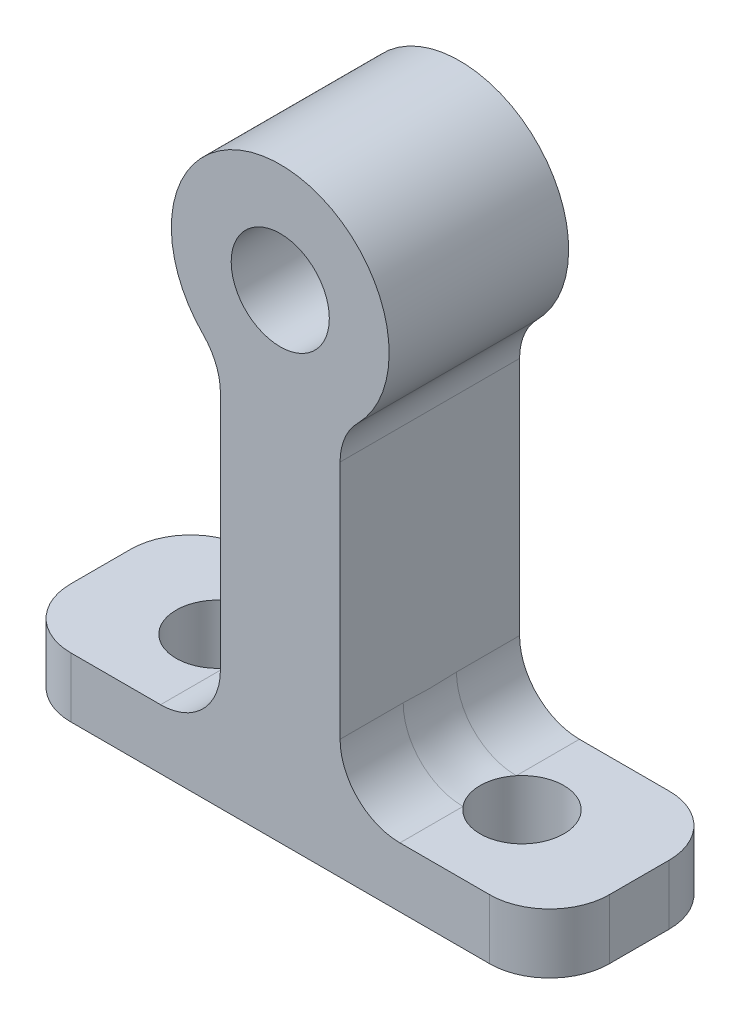
SolidWorks part; units mm, degrees
ref_plane "Front Plane" through (0, 0, 0) normal (0, 0, 1) x (1, 0, 0)
ref_plane "Top Plane" through (0, 0, 0) normal (0, 1, 0) x (1, 0, 0)
ref_plane "Right Plane" through (0, 0, 0) normal (1, 0, 0) x (0, 0, -1)
sketch "Sketch1" plane through (0, 0, 0) normal (0, 0, 1) x (1, 0, 0)
  line L0 (-5, -7.6033) -> (-5, -35)
  line L1 (5, -7.6033) -> (5, -35)
  line L10 (-22.5, -35) -> (-22.5, -40)
  line L11 (-22.5, -40) -> (22.5, -40)
  line L12 (22.5, -35) -> (22.5, -40)
  line L13 (-22.5, -35) -> (-5, -35)
  line L14 (22.5, -35) -> (5, -35)
  arc A1 (5, -7.6033) -> (-5, -7.6033) centre (0, 0) ccw
  circle A2 centre (0, 0) radius 4.1
  point P11 (-7.5, -6.6854)
  dimension "D1" = 8.2
  dimension "D2" = 45
  dimension "D5" = 5
  dimension "D6" = 5
  dimension "D3" = 40
  dimension "D4" = 10
extrude "Boss-Extrude1" add sketch "Sketch1" along normal blind 15
sketch "Sketch4" plane through (0, 0, 0) normal (0, 0, -1) x (-1, 0, 0)
  circle A0 centre (0, 0) radius 4.1
  circle A1 centre (0, 0) radius 4.1 construction
extrude "Boss-Extrude3" add sketch "Sketch4" against normal blind 5
sketch "Sketch5" plane through (0, -40, 0) normal (0, -1, 0) x (1, 0, 0)
  line L0 (0, 0) -> (0, 50000) construction
  line L1 (-22.5, 15) -> (-22.5, 0) construction
  circle A0 centre (-12.7, 7.5) radius 3.5
  circle A1 centre (12.7, 7.5) radius 3.5
  point P5 (-22.5, 7.5)
  point P6 (0, 0)
  dimension "D2" = 7
  dimension "D1" = 25.4
extrude "Cut-Extrude1" cut sketch "Sketch5" against normal up to next
fillet "Fillet1" radius 5 8 edges at (-5, -7.6033, 7.5) (5, -7.6033, 7.5) (5, -35, 7.5) (22.5, -37.5, 0) (22.5, -37.5, 15) (-22.5, -37.5, 0) (-22.5, -37.5, 15) (-5, -35, 7.5)
